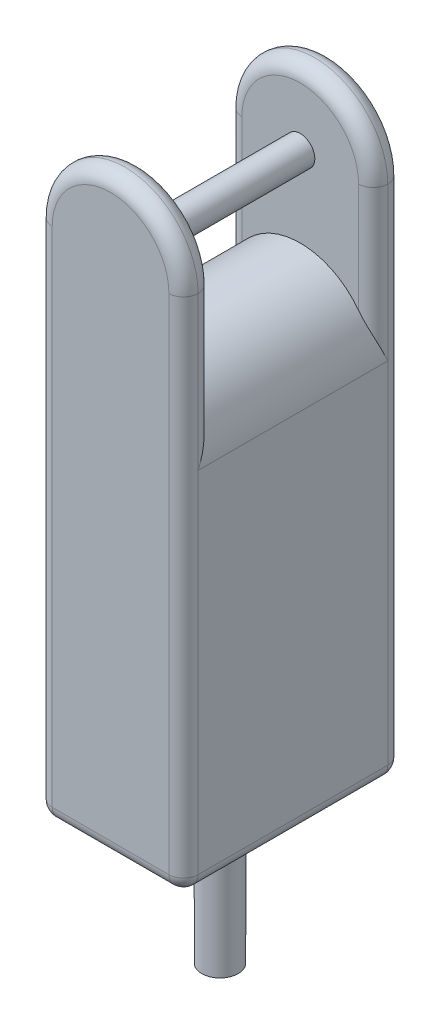
SolidWorks part; units mm, degrees
ref_plane "Front Plane" through (0, 0, 0) normal (0, 0, 1) x (1, 0, 0)
ref_plane "Top Plane" through (0, 0, 0) normal (0, 1, 0) x (1, 0, 0)
ref_plane "Right Plane" through (0, 0, 0) normal (1, 0, 0) x (0, 0, -1)
sketch "Sketch2" plane through (0, 0, 0) normal (0, 0, 1) x (1, 0, 0)
  line L0 (-50, 150) -> (-50, 205)
  line L1 (-50, 150) -> (50, 150)
  line L2 (-50, 150) -> (-50, -150)
  line L3 (-50, -150) -> (50, -150)
  line L4 (50, 150) -> (50, -150)
  line L5 (-50, 150) -> (50, -150) construction
  line L6 (-50, -150) -> (50, 150) construction
  line L8 (50, 150) -> (50, 205)
  arc A0 (-50, 205) -> (50, 205) centre (0, 205) cw
  point P0 (0, 0)
  dimension "D1" = 300
  dimension "D2" = 100
  dimension "D3" = 55
  dimension "D4" = 55
extrude "Boss-Extrude1" add sketch "Sketch2" along normal mid plane 150 contours L4 L1 L2 L3 | A0 L0 L1 L8 region at (0, 197.7955, 0) region at (0, 0, 0)
sketch "Sketch3" plane through (0, 0, 0) normal (0, 1, 0) x (1, 0, 0)
  line L1 (-50, 55) -> (50, 55)
  line L2 (-50, 55) -> (-50, -55)
  line L3 (-50, -55) -> (50, -55)
  line L4 (50, 55) -> (50, -55)
  line L5 (-50, 55) -> (50, -55) construction
  line L6 (-50, -55) -> (50, 55) construction
  point P0 (0, 0)
  dimension "D1" = 110
  dimension "D2" = 100
extrude "Cut-Extrude1" cut sketch "Sketch3" along normal up to surface (55 mm away) from offset 150 up to face at (0, 230, 0)
sketch "Sketch4" plane through (0, 0, -55) normal (0, 0, 1) x (1, 0, 0)
  circle A0 centre (0, 205) radius 10
  dimension "D1" = 20
extrude "Boss-Extrude2" add sketch "Sketch4" along normal up to surface (110 mm away) up to face at (0, 190, 55)
sketch "Sketch5" plane through (0, -150, 0) normal (0, -1, 0) x (1, 0, 0)
  circle A0 centre (0, 0) radius 12.5
  dimension "D1" = 25
extrude "Boss-Extrude3" add sketch "Sketch5" along normal blind 100
fillet "Fillet1" 2 edges at (-50, 150, 0) (50, 150, 0) type full round first side face at (-50, 102.5, 0) second side face at (50, 102.5, 0) middle face at (0, 150, 0)
fillet "Fillet2" radius 10 10 edges at (-50, 27.5, -75) (0, 255, -75) (-50, 27.5, 75) (0, 255, 75) (-50, -150, 0) (0, -150, 75) (50, -150, 0) (0, -150, -75) (50, 27.5, -75) (50, 27.5, 75)
fillet "Fillet3" radius 10 6 edges at (50, 152.5, 55) (0, 255, 55) (50, 152.5, -55) (0, 255, -55) (-50, 152.5, 55) (-50, 152.5, -55)
